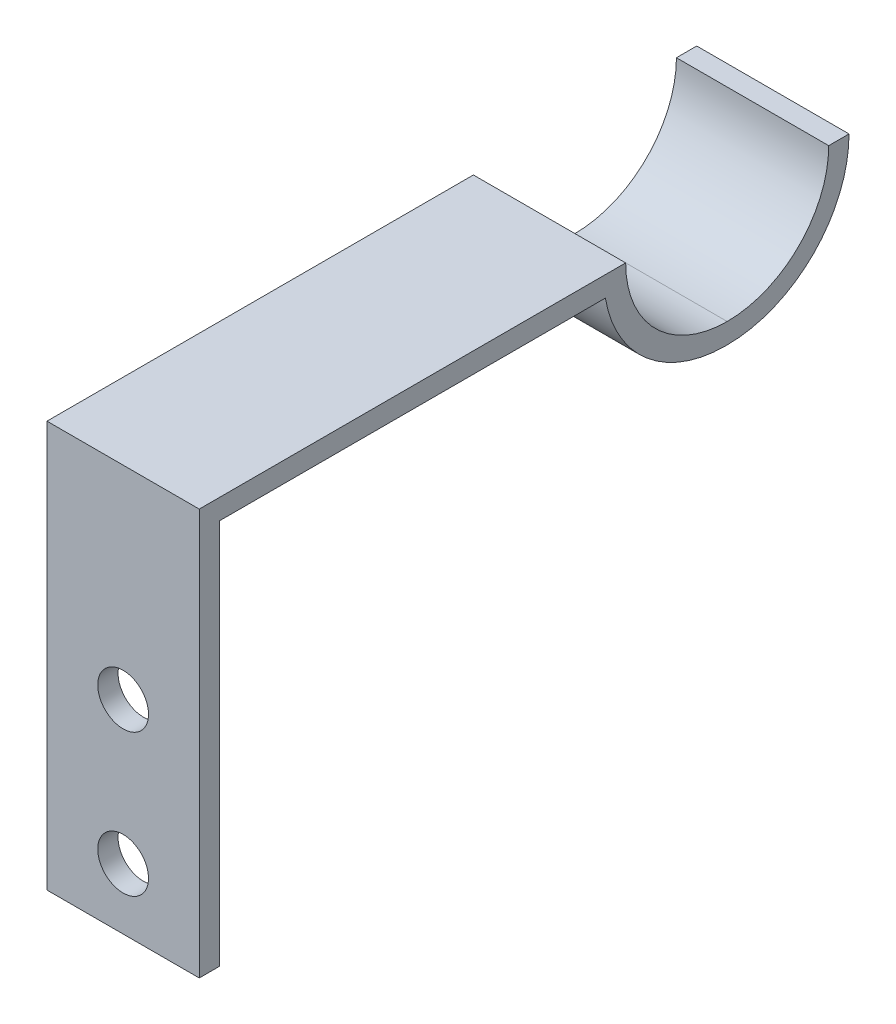
SolidWorks part; units mm, degrees
material "Galvanized Steel"
ref_plane "Front Plane" through (0, 0, 0) normal (0, 0, 1) x (1, 0, 0)
ref_plane "Top Plane" through (0, 0, 0) normal (0, 1, 0) x (1, 0, 0)
ref_plane "Right Plane" through (0, 0, 0) normal (1, 0, 0) x (0, 0, -1)
sketch "Sketch1" plane through (0, 0, 0) normal (0, 0, 1) x (1, 0, 0)
  line L5 (-174.6004, 59.2667) -> (-155.5504, 59.2667)
  line L6 (-174.6004, 59.2667) -> (-174.6004, 8.4667)
  line L7 (-174.6004, 8.4667) -> (-155.5504, 8.4667)
  line L8 (-155.5504, 59.2667) -> (-155.5504, 8.4667)
  circle A0 centre (-165.0754, 16.0867) radius 3.175
  circle A1 centre (-165.0754, 33.8667) radius 3.175
  dimension "D3" = 9.525
  dimension "D1" = 50.8
  dimension "D2" = 19.05
  dimension "D4" = 7.62
  dimension "D5" = 9.525
  dimension "D6" = 25.4
extrude "Boss-Extrude1" add sketch "Sketch1" along normal blind 2.54
sketch "Sketch2" plane through (0, 0, 0) normal (0, 0, -1) x (-1, 0, 0)
  line L0 (155.5504, 56.7267) -> (174.6004, 56.7267)
  line L1 (155.5504, 8.4667) -> (155.5504, 59.2667) construction
  line L2 (174.6004, 59.2667) -> (174.6004, 8.4667) construction
  line L3 (155.5504, 59.2667) -> (174.6004, 59.2667) construction
  line L8 (174.6004, 8.4667) -> (174.6004, 59.2667)
  line L9 (174.6004, 59.2667) -> (155.5504, 59.2667)
  line L10 (155.5504, 59.2667) -> (155.5504, 8.4667)
  line L11 (155.5504, 8.4667) -> (174.6004, 8.4667)
  line L12 (174.6004, 56.7267) -> (174.6004, 59.2667)
  line L13 (174.6004, 59.2667) -> (155.5504, 59.2667)
  line L14 (155.5504, 59.2667) -> (155.5504, 56.7267)
  dimension "D1" = 2.54
  dimension "D2" = 0
extrude "Boss-Extrude2" add sketch "Sketch2" along normal blind 50.8
sketch "Sketch4" plane through (-155.5504, 0, 0) normal (1, 0, 0) x (0, 0, -1)
  line L0 (48.26, 56.7267) -> (48.26, 44.0267)
  line L1 (50.8, 56.7267) -> (0, 56.7267) construction
  line L2 (50.8, 56.7267) -> (50.8, 46.5667)
  line L3 (50.8, 46.5667) -> (76.2, 46.5667)
  line L4 (76.2, 46.5667) -> (76.2, 59.2667)
  line L5 (48.26, 44.0267) -> (78.74, 44.0267)
  line L6 (78.74, 44.0267) -> (78.74, 59.2667)
  line L7 (76.2, 59.2667) -> (78.74, 59.2667)
  line L8 (48.26, 56.7267) -> (50.8, 56.7267)
  dimension "D1" = 2.54
extrude "Boss-Extrude5" add sketch "Sketch4" against normal blind 19.05
fillet "Fillet6" radius 12.7 1 edges at (-165.0754, 46.5667, -50.8)
fillet "Fillet7" radius 15.24 1 edges at (-165.0754, 44.0267, -48.26)
fillet "Fillet11" radius 12.7 1 edges at (-165.0754, 46.5667, -76.2)
fillet "Fillet12" radius 15.24 1 edges at (-165.0754, 44.0267, -78.74)
